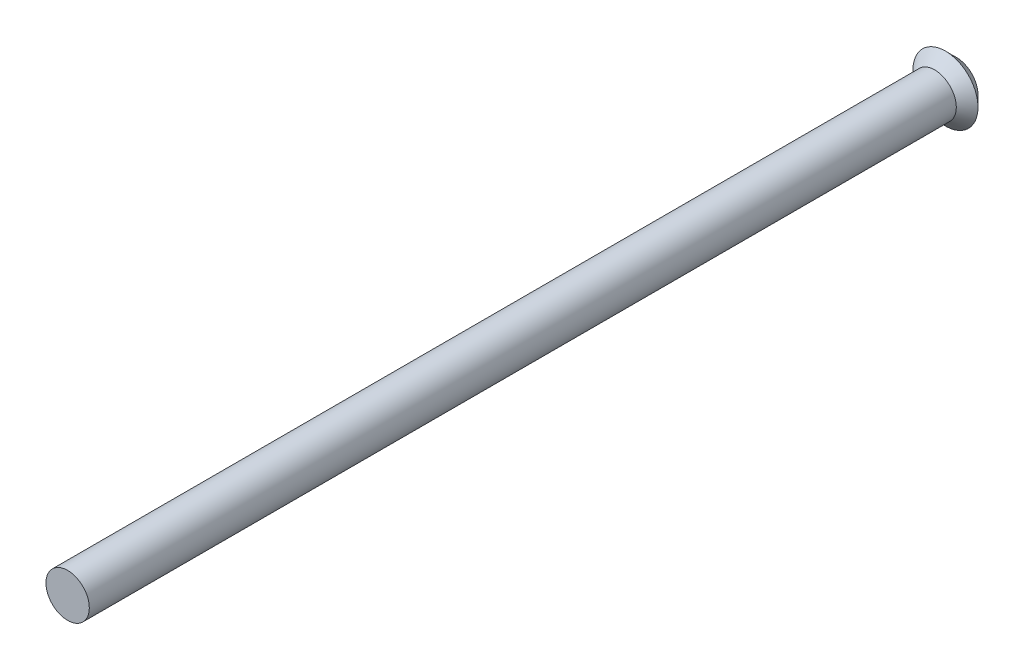
SolidWorks part; units mm, degrees
ref_plane "Front Plane" through (0, 0, 0) normal (0, 0, 1) x (1, 0, 0)
ref_plane "Top Plane" through (0, 0, 0) normal (0, 1, 0) x (1, 0, 0)
ref_plane "Right Plane" through (0, 0, 0) normal (1, 0, 0) x (0, 0, -1)
sketch "Sketch1" plane through (0, 0, 0) normal (0, 1, 0) x (1, 0, 0)
  line L0 (-6, 0) -> (6, 0) construction
  line L1 (6, -20) -> (-6, -20)
  line L2 (6, -20) -> (6, 20)
  line L3 (6, 20) -> (-6, 20)
  line L4 (-6, -20) -> (-6, 20)
  line L5 (6, -20) -> (-6, 20) construction
  line L6 (6, 20) -> (-6, -20) construction
  line L7 (0, -5) -> (0, 5) construction
  circle A0 centre (0, 5) radius 1
  circle A1 centre (0, -5) radius 1
  point P0 (0, 0)
  dimension "D3" = 5
  dimension "D4" = 2
  dimension "D1" = 40
  dimension "D2" = 12
extrude "Hinge " [suppressed] add sketch "Sketch1" along normal blind 5
sketch "Sketch2" [suppressed] plane through (6, 0, 0) normal (1, 0, 0) x (0, 0, -1)
  line L0 (0, 0) -> (0, 5) construction
  line L1 (-20, 0) -> (20, 0) construction
  line L2 (-20, 5) -> (20, 5) construction
  line L3 (-20, 2.5) -> (20, 2.5) construction
  line L4 (-20, 5) -> (-20, 0) construction
  line L5 (20, 5) -> (20, 0) construction
  line L7 (-6, 0) -> (-16, 0)
  line L8 (-6, 0) -> (-6, 5)
  line L9 (-6, 5) -> (-16, 5)
  line L10 (-16, 0) -> (-16, 5)
  line L11 (-6, 0) -> (-16, 5) construction
  line L12 (-6, 5) -> (-16, 0) construction
  line L13 (16, 0) -> (6, 0)
  line L14 (16, 0) -> (16, 5)
  line L15 (16, 5) -> (6, 5)
  line L16 (6, 0) -> (6, 5)
  line L17 (16, 0) -> (6, 5) construction
  line L18 (16, 5) -> (6, 0) construction
  point P12 (-11, 2.5)
  point P17 (11, 2.5)
  dimension "D1" = 6
  dimension "D2" = 5
  dimension "D3" = 10
extrude "Hinge Extrude 1" [suppressed] add sketch "Sketch2" along normal blind 5
sketch "Sketch3" [suppressed] plane through (0, 0, -16) normal (0, 0, -1) x (-1, 0, 0)
  line L0 (-8.5, 0) -> (-8.5, 5) construction
  line L1 (-11, 0) -> (-6, 0) construction
  line L2 (-11, 5) -> (-6, 5) construction
  circle A0 centre (-8.5, 2.5) radius 1
  dimension "D1" = 2
extrude "Hole Cut 1" [suppressed] cut sketch "Sketch3" against normal through all both and the other way through all
fillet "Fillet Holes 1" [suppressed] radius 0.5
chamfer "Chamfer 1" [suppressed] distance 1.5 angle 45
sketch "Sketch4" [suppressed] plane through (6, 0, 0) normal (1, 0, 0) x (0, 0, -1)
  line L0 (0, 0) -> (0, 5) construction
  line L1 (-20, 0) -> (20, 0) construction
  line L2 (-20, 5) -> (20, 5) construction
  line L4 (5, 0) -> (-5, 0)
  line L5 (5, 0) -> (5, 5)
  line L6 (5, 5) -> (-5, 5)
  line L7 (-5, 0) -> (-5, 5)
  line L8 (5, 0) -> (-5, 5) construction
  line L9 (5, 5) -> (-5, 0) construction
  point P6 (0, 2.5)
  dimension "D1" = 5
  dimension "D2" = 10
extrude "Hinge Extrude 2" [suppressed] add sketch "Sketch4" along normal blind 5
sketch "Sketch6" [suppressed] plane through (0, 0, -5) normal (0, 0, -1) x (-1, 0, 0)
  line L0 (-8.5, 0) -> (-8.5, 5) construction
  line L1 (-11, 0) -> (-6, 0) construction
  line L2 (-11, 5) -> (-6, 5) construction
  circle A0 centre (-8.5, 2.5) radius 1
  dimension "D1" = 2
extrude "Hole Cut 2 " [suppressed] cut sketch "Sketch6" against normal through all
chamfer "Chamfer2" [suppressed] distance 1.5 angle 45
fillet "Fillet Holes 2" [suppressed] radius 0.5
sketch "Sketch7" plane through (0, 0, 0) normal (0, 0, 1) x (1, 0, 0)
  circle A0 centre (0, 0) radius 1
  dimension "D1" = 2
extrude "Hinge Holder" add sketch "Sketch7" along normal blind 40
sketch "Sketch8" plane through (0, 0, 0) normal (0, 0, -1) x (-1, 0, 0)
  circle A0 centre (0, 0) radius 1.5
  dimension "D1" = 3
extrude "Hinge Holder Cap" add sketch "Sketch8" along normal blind 1
chamfer "Hinge Holder Cap Fillet" distance 0.5 angle 45 2 edges at (-1.5, 0, 0) (-1.5, 0, -1)
